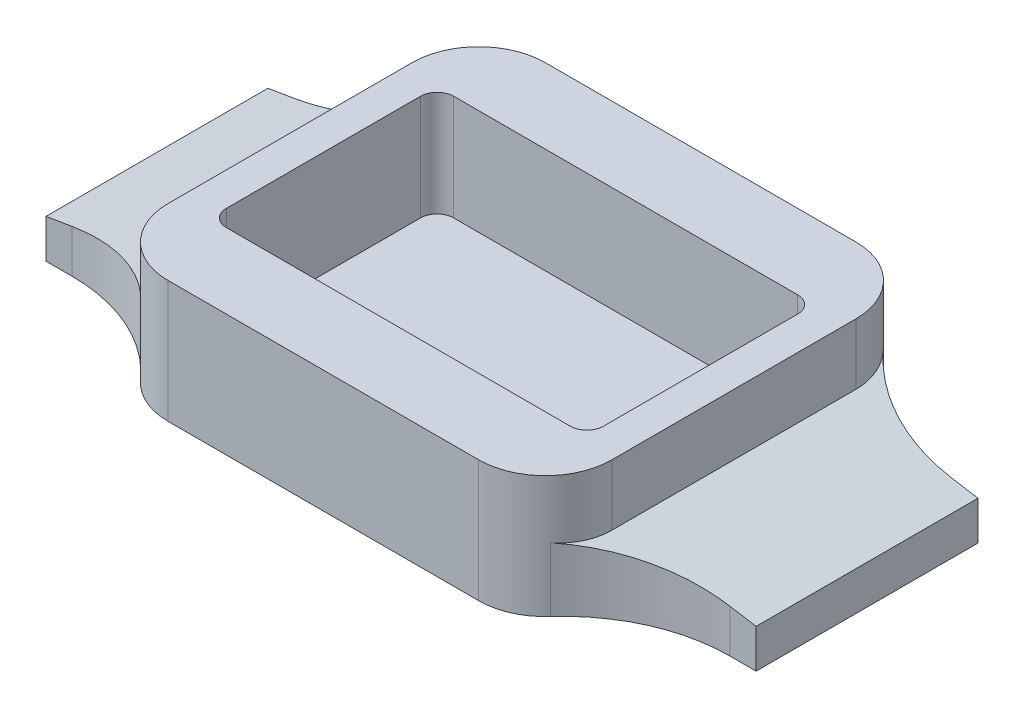
SolidWorks part; units mm, degrees
ref_plane "Front Plane" through (0, 0, 0) normal (0, 0, 1) x (1, 0, 0)
ref_plane "Top Plane" through (0, 0, 0) normal (0, 1, 0) x (1, 0, 0)
ref_plane "Right Plane" through (0, 0, 0) normal (1, 0, 0) x (0, 0, -1)
sketch "Sketch1" plane through (0, 0, 0) normal (0, 1, 0) x (1, 0, 0)
  line L1 (0, 0) -> (40, 0)
  line L2 (0, 0) -> (0, 34)
  line L3 (0, 34) -> (40, 34)
  line L4 (40, 0) -> (40, 34)
  dimension "D1" = 40
  dimension "D2" = 34
extrude "Boss-Extrude1" add sketch "Sketch1" along normal blind 11
sketch "Sketch3" plane through (0, 11, 0) normal (0, 1, 0) x (1, 0, 0)
  line L0 (0, 17) -> (40, 17) construction
  line L1 (0, 34) -> (0, 0) construction
  line L2 (40, 0) -> (40, 34) construction
  line L3 (20, 34) -> (20, 0) construction
  line L4 (40, 34) -> (0, 34) construction
  line L5 (0, 0) -> (40, 0) construction
  line L7 (3, 6.75) -> (37, 6.75)
  line L8 (3, 6.75) -> (3, 27.25)
  line L9 (3, 27.25) -> (37, 27.25)
  line L10 (37, 6.75) -> (37, 27.25)
  line L11 (3, 6.75) -> (37, 27.25) construction
  line L12 (3, 27.25) -> (37, 6.75) construction
  point P12 (20, 17)
  dimension "D1" = 34
  dimension "D2" = 20.5
extrude "Cut-Extrude1" cut sketch "Sketch3" against normal offset from surface (9.5 mm away) 1.5 up to face at (20, 0, -17)
fillet "Fillet2" radius 1.5 4 edges at (3, 6.25, -6.75) (3, 6.25, -27.25) (37, 6.25, -27.25) (37, 6.25, -6.75)
ref_plane "Plane1" through (0, 0, -17) normal (0, 0, -1) x (-1, 0, 0)
sketch "Sketch5" plane through (0, 0, -17) normal (0, 0, -1) x (-1, 0, 0)
  line L0 (-40, 0) -> (-52, 0)
  line L1 (-52, 0) -> (-52, 3.5)
  line L2 (-52, 3.5) -> (-40, 5.5)
  line L3 (-40, 11) -> (-40, 0) construction
  line L4 (-40, 5.5) -> (-40, 0)
  line L5 (-20, 0) -> (-20, 11) construction
  line L6 (0, 0) -> (-40, 0) construction
  line L7 (0, 11) -> (-40, 11) construction
  line L8 (12, 3.5) -> (0, 5.5)
  line L9 (12, 0) -> (12, 3.5)
  line L10 (0, 0) -> (12, 0)
  line L11 (0, 5.5) -> (0, 0)
  dimension "D1" = 12
  dimension "D2" = 3.5
extrude "Boss-Extrude3" add sketch "Sketch5" along normal mid plane 20
fillet "Fillet3" radius 6 4 edges at (40, 5.5, -34) (0, 5.5, -34) (40, 5.5, 0) (0, 5.5, 0)
fillet "Fillet4" radius 15 4 edges at (0, 2.75, -27) (0, 2.75, -7) (40, 2.75, -7) (40, 2.75, -27)
